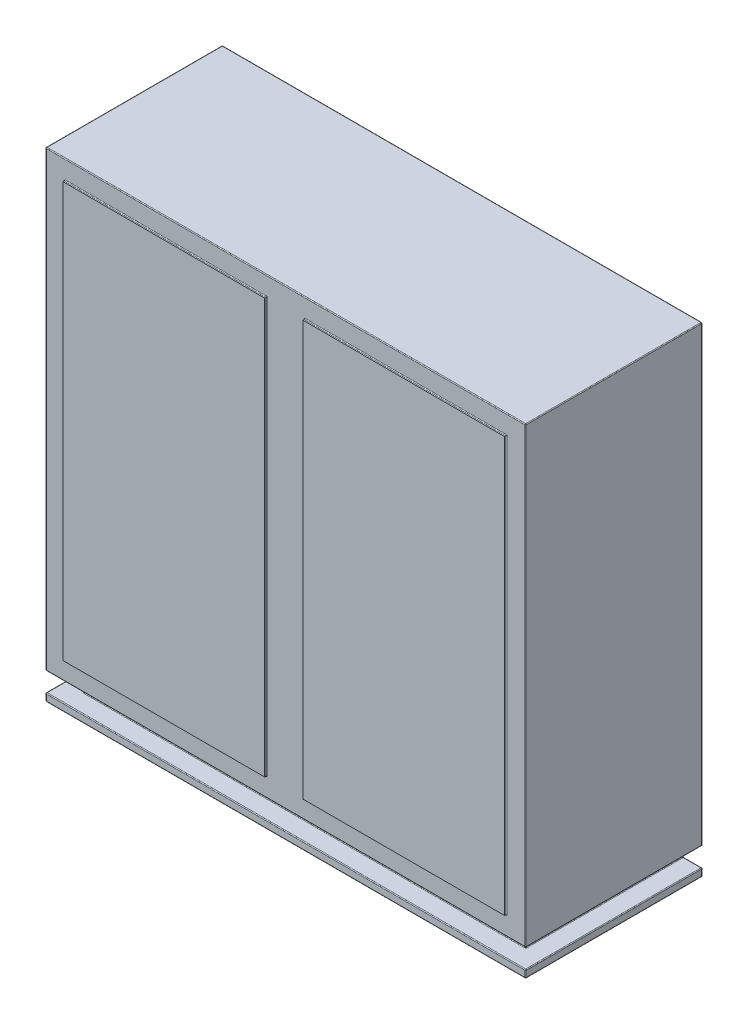
SolidWorks part; units mm, degrees
material "Hêtre"
ref_plane "Plan de face" through (0, 0, 0) normal (0, 0, 1) x (1, 0, 0)
ref_plane "Plan de dessus" through (0, 0, 0) normal (0, 1, 0) x (1, 0, 0)
ref_plane "Plan de droite" through (0, 0, 0) normal (1, 0, 0) x (0, 0, -1)
sketch "Esquisse1" plane through (0, 0, 0) normal (1, 0, 0) x (0, 0, -1)
  line L0 (-230, 0) -> (230, 0)
  line L1 (230, 0) -> (230, 1250)
  line L2 (230, 1250) -> (-230, 1250)
  line L3 (-230, 0) -> (-230, 20)
  line L4 (-230, 20) -> (-180, 20)
  line L5 (-180, 20) -> (-180, 70)
  line L6 (-180, 70) -> (-230, 70)
  line L7 (-230, 70) -> (-230, 1250)
  dimension "D1" = 460
  dimension "D2" = 1180
  dimension "D4" = 20
  dimension "D5" = 50
  dimension "D6" = 50
extrude "Boss.-Extru.1" add sketch "Esquisse1" along normal mid plane 1250
sketch "Esquisse4" plane through (0, 0, 230) normal (0, 0, 1) x (1, 0, 0)
  line L0 (625, 20) -> (-625, 20) construction
  line L1 (-625, 70) -> (-575, 70)
  line L2 (-625, 70) -> (-625, 20)
  line L3 (-625, 20) -> (-575, 20)
  line L4 (-575, 70) -> (-575, 20)
  line L5 (625, 70) -> (-625, 70) construction
  line L6 (625, 20) -> (575, 20)
  line L7 (625, 20) -> (625, 70)
  line L8 (625, 70) -> (575, 70)
  line L9 (575, 20) -> (575, 70)
  dimension "D1" = 50
extrude "Enlèv. mat.-Extru.1" cut sketch "Esquisse4" against normal through all
sketch "Esquisse5" plane through (0, 0, 230) normal (0, 0, 1) x (1, 0, 0)
  line L0 (-625, 1250) -> (-625, 70) construction
  line L1 (-575, 1200) -> (-50, 1200)
  line L2 (-575, 1200) -> (-575, 120)
  line L3 (-575, 120) -> (-50, 120)
  line L4 (-50, 1200) -> (-50, 120)
  line L5 (50, 1200) -> (575, 1200)
  line L6 (50, 1200) -> (50, 120)
  line L7 (50, 120) -> (575, 120)
  line L8 (575, 1200) -> (575, 120)
  line L9 (625, 1250) -> (625, 70) construction
  line L10 (625, 1250) -> (-625, 1250) construction
  line L11 (625, 70) -> (-625, 70) construction
  dimension "D1" = 50
  dimension "D2" = 50
  dimension "D3" = 50
  dimension "D4" = 100
  dimension "D5" = 50
extrude "Boss.-Extru.2" add sketch "Esquisse5" along normal blind 5
fillet "Congé1" radius 2 44 edges at (625, 10, 230) (-625, 10, 230) (0, 0, 230) (625, 0, 0) (-625, 0, 0) (-575, 45, 180) (575, 45, 180) (-575, 20, -25) (0, 20, 180) (575, 20, -25) (625, 20, 0) (0, 20, 230) (-625, 20, 0) (-575, 70, -25) (575, 70, -25) (0, 70, 180) (312.5, 120, 230) (575, 660, 230) (312.5, 1200, 230) (50, 660, 230) (0, 70, 230) (-312.5, 120, 230) (-50, 660, 230) (-312.5, 1200, 230) (-575, 660, 230) (600, 70, -230) (-600, 70, -230) (-575, 45, -230) (-600, 20, -230) (-625, 10, -230) (0, 0, -230) (625, 10, -230) (600, 20, -230) (575, 45, -230) (-625, 660, 230) (-625, 70, 0) (-625, 660, -230) (625, 660, 230) (625, 660, -230) (625, 70, 0) (0, 1250, -230) (625, 1250, 0) (0, 1250, 230) (-625, 1250, 0)
